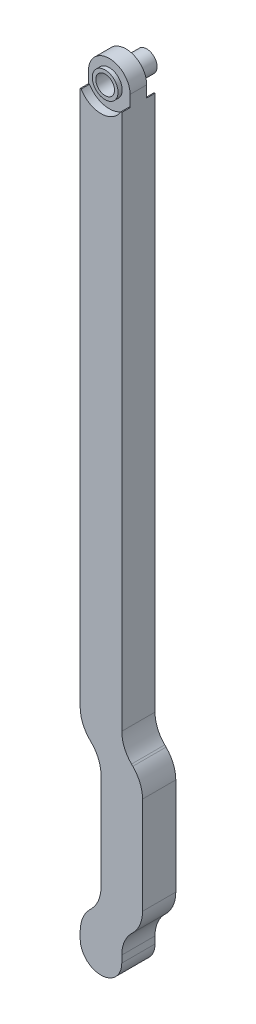
SolidWorks part; units mm, degrees
ref_plane "前视基准面" through (0, 0, 0) normal (0, 0, 1) x (1, 0, 0)
ref_plane "上视基准面" through (0, 0, 0) normal (0, 1, 0) x (1, 0, 0)
ref_plane "右视基准面" through (0, 0, 0) normal (1, 0, 0) x (0, 0, -1)
sketch "草图1" plane through (0, 0, 0) normal (0, 0, 1) x (1, 0, 0)
  line L0 (-5, -175) -> (-5, -180)
  line L1 (-5, -175) -> (0, -170)
  line L2 (0, -170) -> (0, -140)
  line L3 (0, -140) -> (-5, -135)
  line L4 (-5, -135) -> (-5, 0)
  line L8 (5, -135) -> (10, -140)
  line L9 (10, -140) -> (10, -170)
  line L10 (10, -170) -> (5, -175)
  line L12 (5, -180) -> (5, -175)
  line L13 (5, -135) -> (5, 0)
  arc A10 (-5, 0) -> (5, 0) centre (0, 0) cw
  arc A11 (5, -180) -> (-5, -180) centre (0, -180) cw
extrude "凸台-拉伸1" add sketch "草图1" along normal blind 8
fillet "圆角1" radius 8 8 edges at (-5, -135, 4) (0, -140, 4) (0, -170, 4) (-5, -175, 4) (5, -175, 4) (10, -170, 4) (10, -140, 4) (5, -135, 4)
sketch "草图2" plane through (0, 0, 0) normal (0, 0, -1) x (-1, 0, 0)
  line L0 (5, 0) -> (5, -2.75)
  line L4 (4.7631, -2.75) -> (5, -2.75)
  line L5 (5, 0) -> (5, -131.6863) construction
  line L6 (-4.7631, -2.75) -> (-5, -2.75)
  line L7 (-5, -131.6863) -> (-5, 0) construction
  line L8 (-5, -2.75) -> (-5, 0)
  arc A2 (4.7631, -2.75) -> (-4.7631, -2.75) centre (0, 0) cw
  arc A3 (5, 0) -> (-5, 0) centre (0, 0) ccw
extrude "切除-拉伸1" cut sketch "草图2" against normal blind 1
sketch "草图3" plane through (0, 0, 1) normal (0, 0, -1) x (-1, 0, 0)
  circle A0 centre (0, 0) radius 2.5
extrude "凸台-拉伸2" add sketch "草图3" along normal blind 4
sketch "草图4" plane through (0, 0, 1) normal (0, 0, -1) x (-1, 0, 0)
  line L0 (-5, 0) -> (-5, -2.75) construction
  line L1 (-5, 0) -> (-5, -2.75)
  line L2 (-5, -2.75) -> (-4.7631, -2.75)
  line L3 (4.7631, -2.75) -> (5, -2.75)
  line L4 (5, -2.75) -> (5, 0)
  circle A0 centre (0, 0) radius 3.1
  arc A1 (5, 0) -> (-5, 0) centre (0, 0) ccw
  arc A2 (-4.7631, -2.75) -> (4.7631, -2.75) centre (0, 0) ccw
  arc A3 (-4.7631, -2.75) -> (4.7631, -2.75) centre (0, 0) ccw construction
extrude "切除-拉伸3" cut sketch "草图4" against normal blind 1
sketch "草图5" plane through (0, 0, 8) normal (0, 0, 1) x (1, 0, 0)
  circle A0 centre (0, 0) radius 2.25
extrude "切除-拉伸4" cut sketch "草图5" against normal up to next
extrude "切除-拉伸5" cut sketch "草图4<2>" along normal blind 2 from surface starting at face at (2.25, 0, 8)
sketch "草图4<2>" plane through (0, 0, 1) normal (0, 0, -1) x (-1, 0, 0) same geometry as "草图4"
sketch "草图7" plane through (0, 0, 8) normal (0, 0, 1) x (1, 0, 0)
  circle A0 centre (0, 0) radius 3.1
extrude "切除-拉伸6" cut sketch "草图7" against normal blind 1
